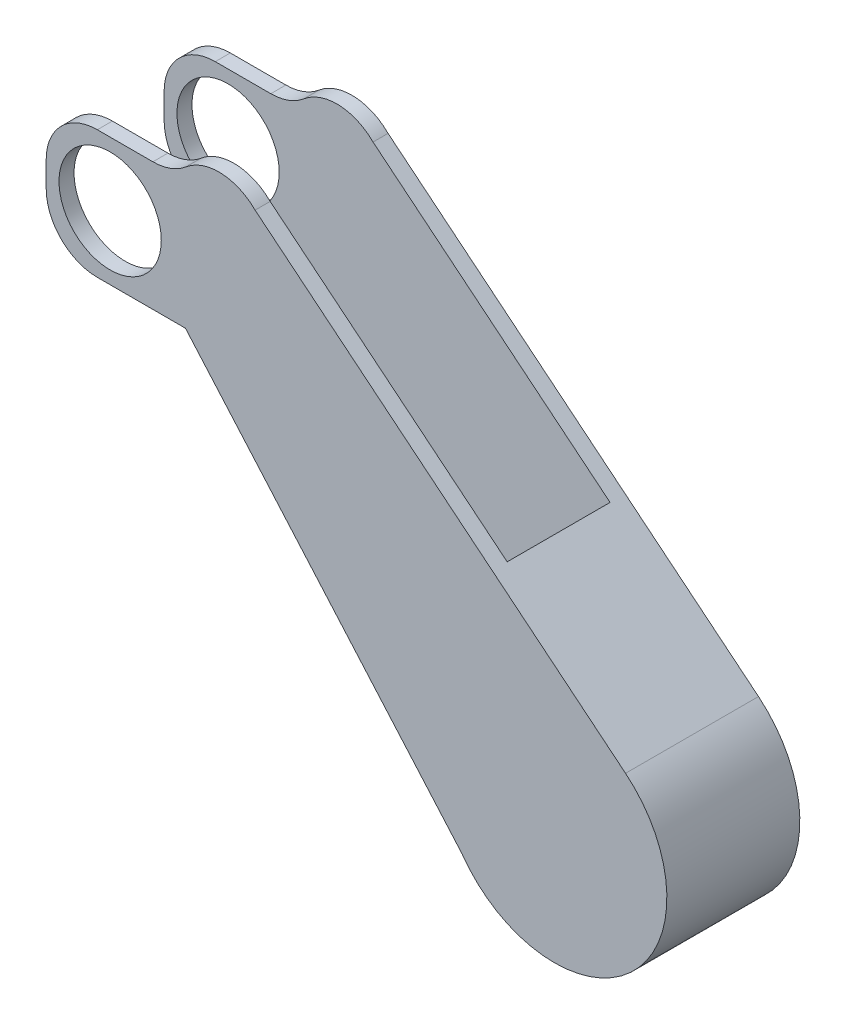
SolidWorks part; units mm, degrees
material "1060 合金"
ref_plane "前视基准面" through (0, 0, 0) normal (0, 0, 1) x (1, 0, 0)
ref_plane "上视基准面" through (0, 0, 0) normal (0, 1, 0) x (1, 0, 0)
ref_plane "右视基准面" through (0, 0, 0) normal (1, 0, 0) x (0, 0, -1)
other "Configuration Table"
sketch "草图1" plane through (0, 0, 0) normal (0, 0, 1) x (1, 0, 0)
  line L0 (0, 0) -> (60.0041, 0)
  line L1 (55, 0) -> (-55, 0) construction
  line L2 (0, 0) -> (-59.9983, 0)
  line L3 (-59.9983, 0) -> (-59.9983, 25.003)
  line L4 (-59.9983, 25.003) -> (60.0041, 25.003)
  line L5 (60.0041, 25.003) -> (60.0041, 0)
extrude "凸台-拉伸1" add sketch "草图1" along normal blind 26
sketch "草图4" plane through (0, 0, 26) normal (0, 0, 1) x (1, 0, 0)
  circle A0 centre (-47.4977, 12.5015) radius 9.9969
extrude "切除-拉伸2" cut sketch "草图4" against normal blind 26
fillet "圆角1" radius 10 1 edges at (-59.9983, 25.003, 13)
fillet "圆角2" radius 10 1 edges at (-59.9983, 0, 13)
sketch "草图7" plane through (0, 25.003, 0) normal (0, 1, 0) x (1, 0, 0)
  line L0 (-37.5015, -23.0585) -> (-36.4011, -23.0585)
  line L4 (-37.5015, -2.94) -> (-62.0536, -2.94)
  line L5 (-62.0536, -2.94) -> (-62.0536, -23.0585)
  line L6 (-62.0536, -23.0585) -> (-37.5015, -23.0585)
  line L7 (-36.4011, -23.0585) -> (-36.4011, -2.94)
  line L8 (-36.4011, -2.94) -> (-37.5015, -2.94)
extrude "切除-拉伸4" cut sketch "草图7" against normal blind 26
sketch "草图8" plane through (0, 0, 2.94) normal (0, 0, 1) x (1, 0, 0)
  circle A0 centre (-47.4977, 12.5015) radius 13.6
extrude "切除-拉伸5" cut sketch "草图8" along normal blind 20.12
sketch "草图9" plane through (0, 0, 26) normal (0, 0, 1) x (1, 0, 0)
  line L2 (60.0041, 25.003) -> (-49.9983, 25.003) construction
  line L3 (-34.9989, 25.003) -> (-22.5001, 12.5015)
  line L5 (48.2029, -58.2168) -> (39.3663, -67.0535)
  line L6 (48.2029, -58.2168) -> (57.0397, -49.38)
  line L7 (57.0397, -49.38) -> (-17.3433, 25.003)
  line L8 (-34.9989, 25.003) -> (-26.1711, 33.8308)
  line L9 (-26.1711, 33.8308) -> (-17.3433, 25.003)
  line L10 (39.3663, -67.0535) -> (-27.6872, 0)
  line L11 (-49.9983, 0) -> (60.0041, 0) construction
  line L12 (-27.6872, 0) -> (-22.5001, 12.5015)
extrude "凸台-拉伸2" add sketch "草图9" against normal up to surface (26 mm away) up to face at (-37.5008, 12.5015, 0)
fillet "圆角3" radius 3 3 edges at (-36.4011, 0, 12.9992) (-36.4011, 20.3645, 12.9992) (-36.4011, 4.6385, 12.9992)
sketch "草图10" plane through (0, 0, 26) normal (0, 0, 1) x (1, 0, 0)
  line L0 (7.6597, 0) -> (60.0041, 0)
  line L1 (60.0041, 0) -> (60.0041, 25.003)
  line L2 (60.0041, 25.003) -> (-17.3433, 25.003)
  line L3 (-17.3433, 25.003) -> (7.6597, 0)
extrude "切除-拉伸6" cut sketch "草图10" against normal blind 30
fillet "圆角9" radius 10 1 edges at (-34.9989, 25.003, 13)
fillet "圆角10" radius 3 1 edges at (-36.4011, 25.3857, 12.9992)
fillet "圆角11" radius 10 1 edges at (-26.1711, 33.8308, 13)
sketch "草图12" plane through (3.8299, 3.8299, 0) normal (0.7071, 0.7071, 0) x (0, 0, -1)
  line L0 (-12.9992, 43.1212) -> (-9.9981, 43.1212)
  line L1 (-2.94, 43.1212) -> (-23.0585, 43.1212) construction
  line L2 (-12.9992, 43.1212) -> (-15.9955, 43.1212)
  line L3 (-15.9955, 43.1212) -> (-15.9955, 23.1189)
  line L4 (-15.9955, 23.1189) -> (-9.9981, 23.1189)
  line L5 (-9.9981, 23.1189) -> (-9.9981, 43.1212)
extrude "切除-拉伸7" cut sketch "草图12" against normal blind 30
sketch "草图13" plane through (3.8299, 3.8299, 0) normal (0.7071, 0.7071, 0) x (0, 0, -1)
  line L0 (-23.0585, 42.9611) -> (-23.0585, -27.0389)
  line L1 (-2.94, 42.9611) -> (-2.94, -27.0389)
  line L2 (-2.94, -27.0389) -> (-23.0585, -27.0389)
  line L3 (-23.0585, 42.9611) -> (-2.94, 42.9611)
extrude "切除-拉伸8" cut sketch "草图13" against normal mid plane 89.5
sketch "草图14" plane through (3.8299, 3.8299, 0) normal (0.7071, 0.7071, 0) x (0, 0, -1)
  line L0 (-23.06, 55.9628) -> (-23.0585, 36.0598)
  line L1 (-23.0585, 32.4966) -> (-23.0585, 42.4621) construction
  line L2 (-23.0585, 36.0598) -> (-2.94, 36.0598)
  line L3 (-2.94, 42.4621) -> (-2.94, 32.4966) construction
  line L4 (-2.94, 36.0598) -> (-2.94, 55.9628)
  line L5 (-2.94, 55.9628) -> (-23.06, 55.9628)
extrude "切除-拉伸9" cut sketch "草图14" against normal mid plane 89.5
sketch "草图15" plane through (0, 0, 0) normal (0, 0, -1) x (-1, 0, 0)
  circle A0 centre (-39.3663, -49.38) radius 22
extrude "凸台-拉伸3" add sketch "草图15" against normal up to surface (26 mm away) up to face at (-24.6067, 1.482, 26)
sketch "草图16" plane through (0, 0, 26) normal (0, 0, 1) x (1, 0, 0)
  line L0 (53.2816, -32.34) -> (-19.1487, 26.8084)
  line L1 (35.4002, -27.7405) -> (-19.1487, 26.8084)
  arc A1 (17.7267, -45.4139) -> (35.4002, -27.7405) centre (39.3663, -49.38) ccw construction
  arc A2 (53.2816, -32.34) -> (35.4002, -27.7405) centre (39.3663, -49.38) ccw
extrude "凸台-拉伸4" add sketch "草图16" against normal up to surface (26 mm away) up to face at (-26.0987, 2.974, 0)
sketch "草图17" plane through (3.8299, 3.8299, 0) normal (-0.7071, -0.7071, 0) x (0, 0, 1)
  line L1 (23.0585, 32.4966) -> (23.0585, -27.0389)
  line L2 (23.0585, -27.0389) -> (2.94, -27.0389)
  line L3 (2.94, -27.0389) -> (2.94, 32.4289)
  line L4 (2.94, 32.4289) -> (2.94, 35.3541)
  line L5 (2.94, 35.3541) -> (23.06, 35.3541)
  line L6 (23.06, 35.3541) -> (23.0585, 32.4966)
extrude "切除-拉伸13" cut sketch "草图17" against normal blind 20
sketch "草图19" plane through (0, 0, 26) normal (0, 0, 1) x (1, 0, 0)
  line L1 (14.3, 0) -> (-14.3, 0) construction
  line L2 (-32.7635, 0) -> (-27.6872, 0)
  line L3 (17.7267, -45.4139) -> (-27.6872, 0)
  line L5 (-32.7635, 0) -> (21.3589, -62.0186)
  arc A0 (17.7267, -45.4139) -> (53.2816, -32.34) centre (39.3663, -49.38) ccw construction
  arc A2 (17.7267, -45.4139) -> (21.3589, -62.0186) centre (39.3663, -49.38) ccw
extrude "凸台-拉伸5" add sketch "草图19" against normal up to surface (2.9415 mm away) up to face at (-15.697, 3.834, 23.0585)
sketch "草图20" plane through (0, 0, 0) normal (0, 0, -1) x (-1, 0, 0)
  line L0 (-21.3589, -62.0186) -> (32.7635, 0) construction
  line L1 (-17.7267, -45.4139) -> (27.6872, 0)
  line L2 (27.6872, 0) -> (32.7635, 0)
  line L3 (14.3, 0) -> (-14.3, 0) construction
  line L4 (32.7635, 0) -> (-21.3589, -62.0186)
  arc A0 (-17.7267, -45.4139) -> (-21.3589, -62.0186) centre (-39.3663, -49.38) cw
extrude "凸台-拉伸6" add sketch "草图20" against normal up to surface (2.94 mm away) up to face at (-30.9999, 8.7251, 2.94)
